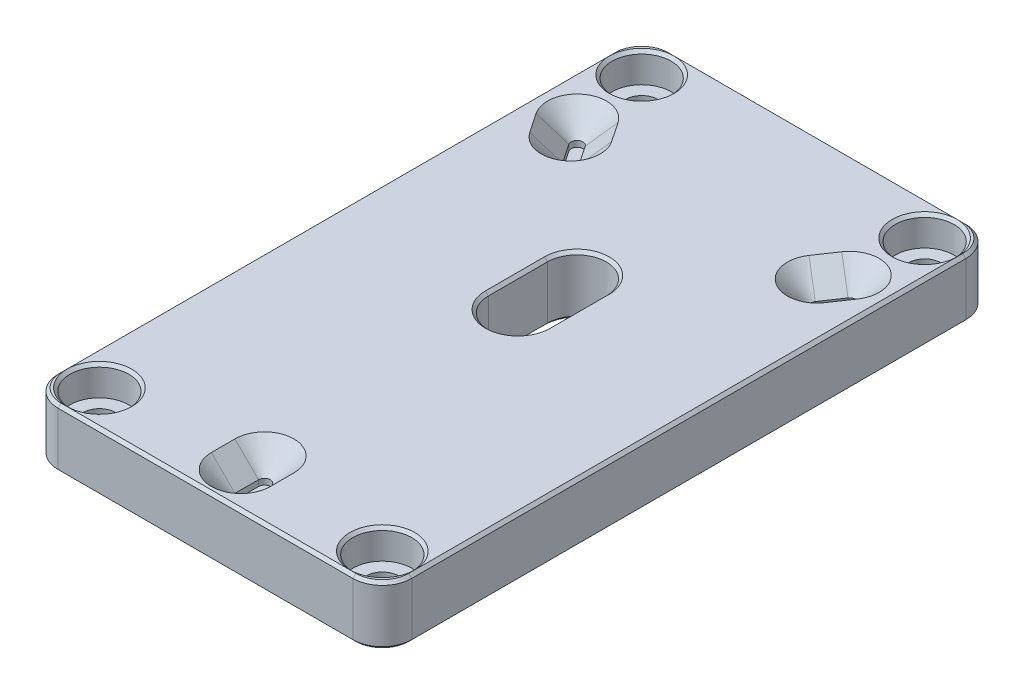
SolidWorks part; units mm, degrees
ref_plane "Front Plane" through (0, 0, 0) normal (0, 0, 1) x (1, 0, 0)
ref_plane "Top Plane" through (0, 0, 0) normal (0, 1, 0) x (1, 0, 0)
ref_plane "Right Plane" through (0, 0, 0) normal (1, 0, 0) x (0, 0, -1)
sketch "Sketch1" plane through (0, 0, 0) normal (0, 1, 0) x (1, 0, 0)
  line L1 (-30, 52) -> (30, 52)
  line L2 (-30, 52) -> (-30, -52)
  line L3 (-30, -52) -> (30, -52)
  line L4 (30, 52) -> (30, -52)
  line L5 (-30, 52) -> (30, -52) construction
  line L6 (-30, -52) -> (30, 52) construction
  point P0 (0, 0)
  dimension "D1" = 60
  dimension "D2" = 104
extrude "Boss-Extrude1" add sketch "Sketch1" along normal blind 10
sketch "Sketch10" plane through (0, 10, 0) normal (0, 1, 0) x (1, 0, 0)
  circle A0 centre (0, -44) radius 2.75 construction
  circle A1 centre (-22, 32.5) radius 2.75 construction
  circle A2 centre (22, 32.5) radius 2.75 construction
  circle A3 centre (0, -44) radius 2.75
  circle A4 centre (-22, 32.5) radius 2.75
  circle A5 centre (22, 32.5) radius 2.75
  circle A6 centre (0, 34) radius 15 construction
  circle A7 centre (0, -21.5) radius 15 construction
  circle A8 centre (0, 34) radius 15
  circle A9 centre (0, -21.5) radius 15
  circle A10 centre (0, 11) radius 1.85 construction
  circle A11 centre (0, 1) radius 1.85 construction
  circle A12 centre (0, 11) radius 1.85
  circle A13 centre (0, 1) radius 1.85
  point P15 (0, 0)
sketch "Sketch3" plane through (0, 10, 0) normal (0, 1, 0) x (1, 0, 0)
  line L0 (0, 0) -> (22, 32.5) construction
  line L1 (0, 0) -> (-22, 32.5) construction
  line L5 (0, 0) -> (0, -44) construction
  line L6 (-23.1211, 34.1562) -> (-20.8789, 30.8438) construction
  line L7 (-22.293, 34.7168) -> (-20.0508, 31.4043)
  line L8 (-23.9492, 33.5957) -> (-21.707, 30.2832)
  line L9 (23.1211, 34.1562) -> (20.8789, 30.8438) construction
  line L10 (23.9492, 33.5957) -> (21.707, 30.2832)
  line L11 (22.293, 34.7168) -> (20.0508, 31.4043)
  line L12 (0, -46) -> (0, -42) construction
  line L13 (-1, -46) -> (-1, -42)
  line L14 (1, -46) -> (1, -42)
  arc A0 (-22.293, 34.7168) -> (-23.9492, 33.5957) centre (-23.1211, 34.1562) ccw
  arc A1 (-21.707, 30.2832) -> (-20.0508, 31.4043) centre (-20.8789, 30.8438) ccw
  arc A2 (23.9492, 33.5957) -> (22.293, 34.7168) centre (23.1211, 34.1562) ccw
  arc A3 (20.0508, 31.4043) -> (21.707, 30.2832) centre (20.8789, 30.8438) ccw
  arc A4 (-1, -46) -> (1, -46) centre (0, -46) ccw
  arc A5 (1, -42) -> (-1, -42) centre (0, -42) ccw
  point P3 (0, -44)
  point P5 (-22, 32.5)
  point P8 (22, 32.5)
  point P19 (-22, 32.5)
  point P25 (22, 32.5)
  point P32 (0, -44)
  point P38 (0, 0)
  dimension "D2" = 1
  dimension "D1" = 4
extrude "Cut-Extrude1" cut sketch "Sketch3" against normal blind 5
chamfer "Chamfer1" distance 4 angle 45 12 edges at (-22.8281, 10, -31.9394) (-20.3183, 10, -30.0157) (-23.6817, 10, -34.9843) (-21.1719, 10, -33.0606) (-1, 10, 44) (0, 10, 47) (0, 10, 41) (1, 10, 44) (21.1719, 10, -33.0606) (20.3183, 10, -30.0157) (23.6817, 10, -34.9843) (22.8281, 10, -31.9394)
sketch "Sketch5" plane through (0, 10, 0) normal (0, 1, 0) x (1, 0, 0)
  circle A2 centre (0, -21.5) radius 15 construction
  circle A3 centre (0, -21.5) radius 15
  circle A4 centre (0, 34) radius 15 construction
  circle A5 centre (0, 34) radius 15
extrude "Cut-Extrude3" cut sketch "Sketch5" against normal through all from offset 1.5 offset against normal yes
sketch "Sketch6" plane through (0, 10, 0) normal (0, 1, 0) x (1, 0, 0)
  line L8 (24, -46) -> (24, 46)
  line L9 (24, 46) -> (-24, 46)
  line L10 (-24, 46) -> (-24, -46)
  line L11 (-24, -46) -> (24, -46)
  line L12 (24, -46) -> (24, 46) construction
  line L13 (24, 46) -> (-24, 46) construction
  line L14 (-24, 46) -> (-24, -46) construction
  line L15 (-24, -46) -> (24, -46) construction
  dimension "D1" = 6
hole_wizard "CBORE for M5 SHCS1" positions "Sketch7" profile "Sketch8" counterbore size "M5" standard "ANSI Metric" end condition through all
sketch "Sketch7" plane through (0, 10, 0) normal (0, 1, 0) x (1, 0, 0)
  point P0 (-24, 46)
  point P3 (24, 46)
  point P6 (24, -46)
  point P9 (-24, -46)
sketch "Sketch8" plane through (-24, 10, -46) normal (1, 0, 0) x (0, 0, 1)
  line L0 (0, 0) -> (0, 10)
  line L1 (0, 10) -> (2.75, 10)
  line L3 (2.75, 10) -> (2.75, 5)
  line L4 (2.75, 5) -> (5, 5)
  line L5 (5, 5) -> (5, 0)
  line L7 (5, 0) -> (0, 0)
  line L11 (0, -6.35) -> (0, 107.95) construction
  dimension "Thru Hole Dia." = 5.5
  dimension "Thru Hole Depth" = 10
  dimension "C'Bore Dia." = 10
  dimension "C'Bore Depth" = 5
fillet "Fillet1" radius 5 4 edges at (30, 5, -52) (30, 5, 52) (-30, 5, 52) (-30, 5, -52)
sketch "Sketch9" plane through (0, 0, 0) normal (0, -1, 0) x (1, 0, 0)
  circle A0 centre (0, -19) radius 0.35
  circle A4 centre (0, -34) radius 15 construction
  point P2 (0, -8.08)
  point P3 (0, -19)
  dimension "D1" = 0.7
extrude "Boss-Extrude2" add sketch "Sketch9" against normal up to next
sketch "Sketch11" plane through (0, 0, 0) normal (0, -1, 0) x (1, 0, 0)
  circle A0 centre (0, 6.5) radius 0.35
  circle A1 centre (0, 21.5) radius 15 construction
  arc A2 (-0.35, -19.0041) -> (0.35, -19.0041) centre (0, -19) ccw construction
extrude "Boss-Extrude3" add sketch "Sketch11" against normal up to next contours A0
pattern_circular "CirPattern1" count 6 over 360 about axis through (0, 0, 21.5) along (0, 1, 0) of "Boss-Extrude3" reverse direction yes
pattern_circular "CirPattern2" count 6 over 360 about axis through (0, 0, -34) along (0, 1, 0) of "Boss-Extrude2" reverse direction yes
sketch "Sketch12" plane through (0, 10, 0) normal (0, 1, 0) x (1, 0, 0)
  line L0 (0, 1) -> (0, 11) construction
  line L1 (-5, 1) -> (-5, 11)
  line L2 (5, 1) -> (5, 11)
  arc A0 (-5, 1) -> (5, 1) centre (0, 1) ccw
  arc A1 (5, 11) -> (-5, 11) centre (0, 11) ccw
  point P4 (0, 6)
  dimension "D1" = 5
extrude "Cut-Extrude4" cut sketch "Sketch12" against normal through all
chamfer "Chamfer2" distance 0.5 angle 45 28 edges at (0, 0, 52) (28.5355, 0, 50.5355) (-28.5355, 0, 50.5355) (30, 0, 0) (-30, 0, 0) (28.5355, 0, -50.5355) (-28.5355, 0, -50.5355) (0, 0, -52) (-5, 0, -6) (0, 0, 4) (0, 0, -16) (5, 0, -6) (24, 10, 51) (-24, 10, 51) (-24, 10, -41) (24, 10, -41) (-5, 10, -6) (0, 10, 4) (0, 10, -16) (5, 10, -6) (-30, 10, 0) (-28.5355, 10, 50.5355) (-28.5355, 10, -50.5355) (0, 10, 52) (0, 10, -52) (28.5355, 10, 50.5355) (28.5355, 10, -50.5355) (30, 10, 0)
